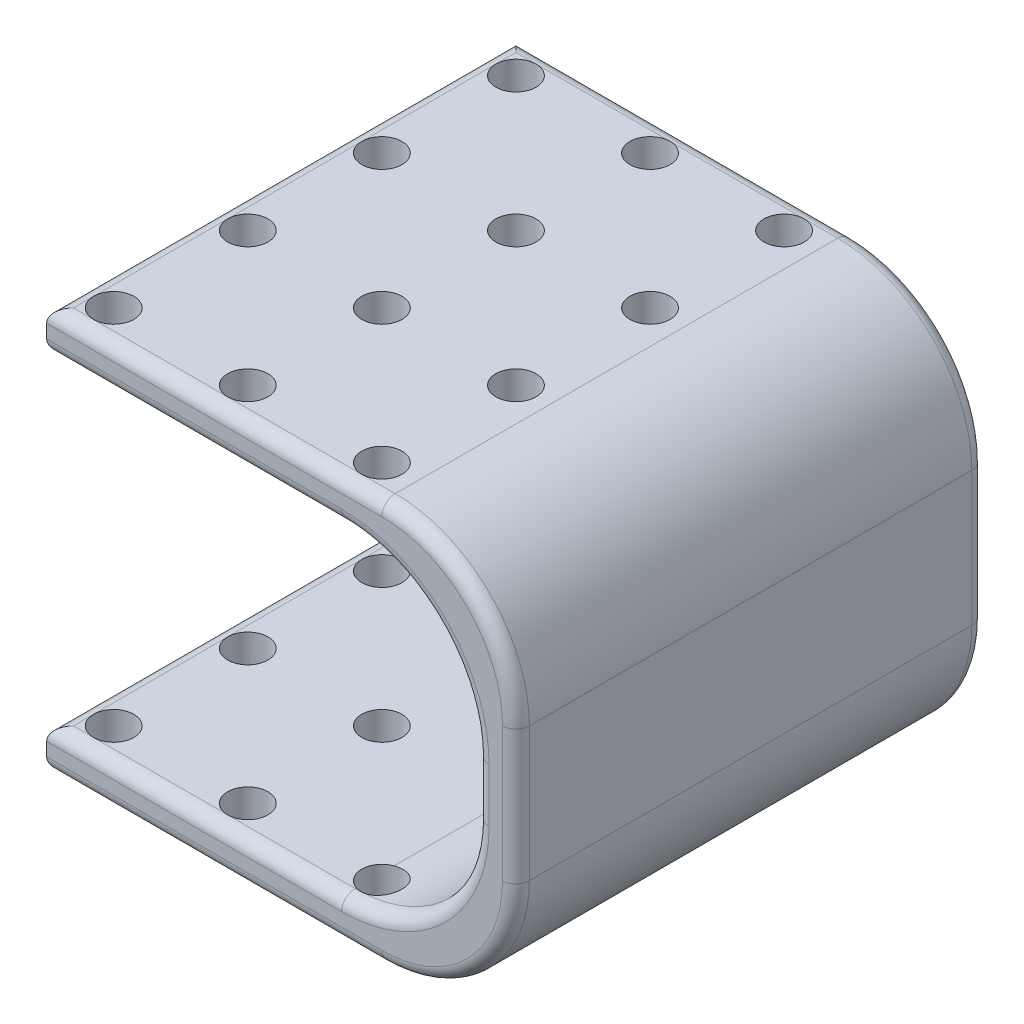
SolidWorks part; units mm, degrees
ref_plane "Plan de face" through (0, 0, 0) normal (0, 0, 1) x (1, 0, 0)
ref_plane "Plan de dessus" through (0, 0, 0) normal (0, 1, 0) x (1, 0, 0)
ref_plane "Plan de droite" through (0, 0, 0) normal (1, 0, 0) x (0, 0, -1)
sketch "Esquisse1" plane through (0, 0, 0) normal (0, 0, 1) x (1, 0, 0)
  line L0 (0, 0) -> (25, 0)
  line L1 (35, 10) -> (35, 20)
  line L2 (25, 30) -> (0, 30)
  line L3 (0, 30) -> (0, 27)
  line L4 (0, 27) -> (22, 27)
  line L5 (32, 17) -> (32, 13)
  line L6 (22, 3) -> (0, 3)
  line L7 (0, 3) -> (0, 0)
  arc A0 (35, 20) -> (25, 30) centre (25, 20) ccw
  arc A1 (25, 0) -> (35, 10) centre (25, 10) ccw
  arc A2 (32, 17) -> (22, 27) centre (22, 17) ccw
  arc A3 (32, 13) -> (22, 3) centre (22, 13) cw
  point P7 (35, 30)
  point P10 (35, 0)
  dimension "D4" = 10
  dimension "D5" = 10
  dimension "D9" = 10
  dimension "D10" = 10
  dimension "D1" = 30
  dimension "D2" = 35
  dimension "D3" = 35
  dimension "D6" = 3
  dimension "D7" = 3
  dimension "D8" = 3
extrude "Boss.-Extru.1" add sketch "Esquisse1" along normal blind 35
sketch "Esquisse2" plane through (0, 30, 0) normal (0, 1, 0) x (1, 0, 0)
  line L0 (25, 0) -> (0, 0) construction
  line L1 (0, -35) -> (0, 0) construction
  circle A0 centre (2.5, -2.5) radius 1.5
  circle A1 centre (12.5, -2.5) radius 1.5
  circle A2 centre (22.5, -2.5) radius 1.5
  circle A3 centre (12.5, -12.5) radius 1.5
  circle A4 centre (22.5, -12.5) radius 1.5
  circle A5 centre (12.5, -22.5) radius 1.5
  circle A6 centre (22.5, -22.5) radius 1.5
  circle A7 centre (12.5, -32.5) radius 1.5
  circle A8 centre (22.5, -32.5) radius 1.5
  circle A9 centre (2.5, -12.5) radius 1.5
  circle A10 centre (2.5, -22.5) radius 1.5
  circle A11 centre (2.5, -32.5) radius 1.5
  dimension "D1" = 3
  dimension "D4" = 2.5
  dimension "D5" = 2.5
  dimension "D2" = 3
  dimension "D3" = 4
extrude "Enlèv. mat.-Extru.1" cut sketch "Esquisse2" against normal blind 73
fillet "Congé3" radius 1 24 edges at (11, 27, 0) (11, 3, 0) (29.0711, 5.9289, 0) (32, 15, 0) (12.5, 0, 0) (32.0711, 2.9289, 0) (35, 15, 0) (32.0711, 27.0711, 0) (11, 3, 35) (29.0711, 5.9289, 35) (32, 15, 35) (29.0711, 24.0711, 35) (12.5, 0, 35) (32.0711, 2.9289, 35) (35, 15, 35) (32.0711, 27.0711, 35) (0, 3, 17.5) (0, 0, 17.5) (29.0711, 24.0711, 0) (12.5, 30, 0) (0, 30, 17.5) (0, 27, 17.5) (11, 27, 35) (12.5, 30, 35)
